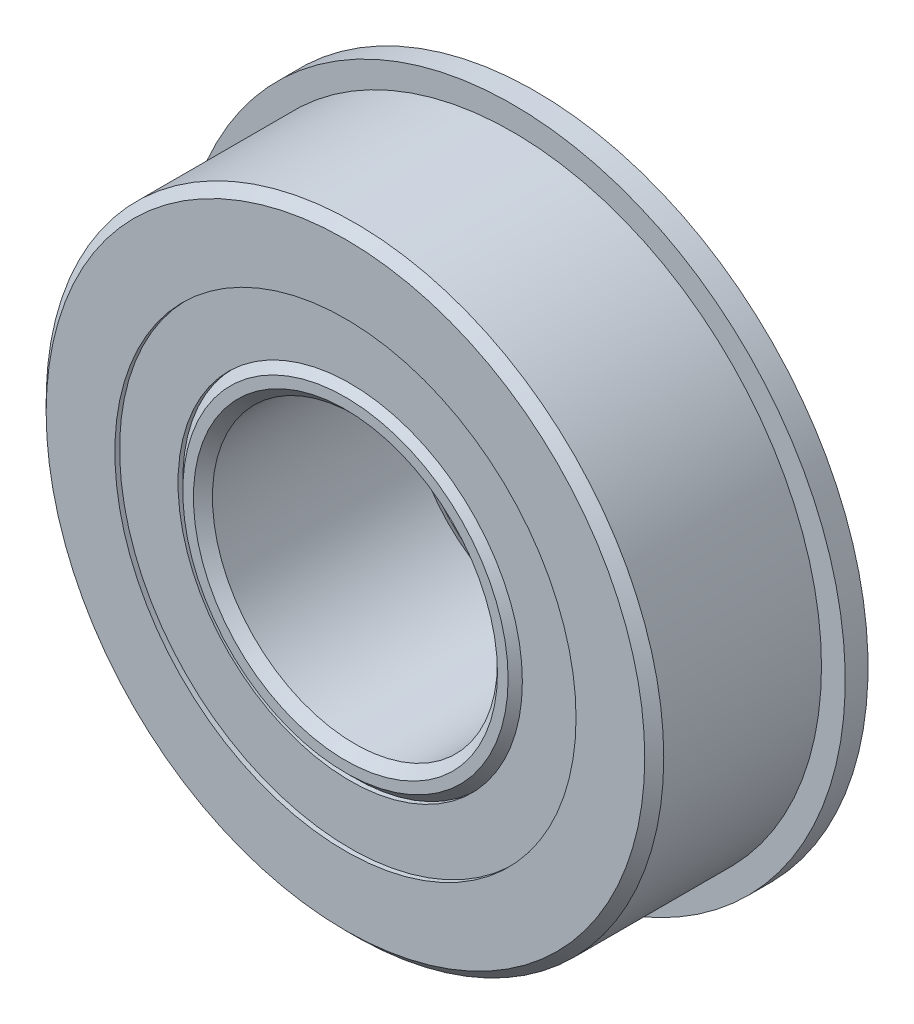
SolidWorks part; units mm, degrees
ref_plane "Front Plane" through (0, 0, 0) normal (0, 0, 1) x (1, 0, 0)
ref_plane "Top Plane" through (0, 0, 0) normal (0, 1, 0) x (1, 0, 0)
ref_plane "Right Plane" through (0, 0, 0) normal (1, 0, 0) x (0, 0, -1)
sketch "Sketch1" plane through (0, 0, 0) normal (1, 0, 0) x (0, 0, -1)
  line L0 (-6.35, 0) -> (6.35, 0) construction
  line L1 (0, 20.6375) -> (0, -20.6375) construction
  line L2 (5.715, 20.6375) -> (-5.715, 20.6375)
  line L3 (-5.715, 20.6375) -> (-6.35, 20.0025)
  line L4 (-6.35, 20.0025) -> (-6.35, 15.4104)
  line L5 (-6.35, 15.4104) -> (-4.2205, 15.4104)
  line L6 (6.35, 15.4104) -> (4.2205, 15.4104)
  line L7 (6.35, 20.0025) -> (6.35, 15.4104)
  line L8 (5.715, 20.6375) -> (6.35, 20.0025)
  line L9 (0, 20.6375) -> (0, 15.0813) construction
  line L10 (0, 15.0813) -> (0, 9.525) construction
  line L11 (6.35, 11.5062) -> (6.35, -11.5062) construction
  line L12 (-6.35, 9.525) -> (6.35, 9.525) construction
  line L13 (0, 10.8479) -> (0, 9.525) construction
  line L14 (0, 19.3146) -> (0, 20.6375) construction
  line L15 (6.35, 11.5062) -> (0, 11.5062) construction
  circle A1 centre (0, 15.0813) radius 4.2333 construction
  arc A2 (-4.2205, 15.4104) -> (4.2205, 15.4104) centre (0, 15.0813) cw
  point P14 (0, 9.525)
  point P22 (0, 10.8479)
  point P23 (0, 19.3146)
  dimension "D3" = 8.4667
  dimension "Width" = 12.7
  dimension "OD" = 41.275
  dimension "D1" = 45
  dimension "D2" = 0.635
  dimension "D4" = 23.0124
  dimension "D5" = 7.8084
  dimension "D6" = 3.9042
revolve "Revolve1" add sketch "Sketch1" angle 360 about L0
sketch "Sketch3" plane through (0, 0, 0) normal (1, 0, 0) x (0, 0, -1)
  line L1 (-6.35, 20.0025) -> (-6.35, 15.4104) construction
  line L2 (-5.715, 20.6375) -> (-6.35, 20.0025) construction
  line L3 (-6.35, 14.7521) -> (-6.35, 10.16) construction
  line L4 (-6.35, 10.16) -> (-6.35, 10.8712)
  line L5 (-6.35, 10.16) -> (-5.715, 9.525)
  line L6 (-5.715, 9.525) -> (7.3152, 9.525)
  line L7 (-6.35, 20.0025) -> (-6.35, -20.0025) construction
  line L8 (7.3152, 9.525) -> (7.9502, 10.16)
  line L9 (0, 0) -> (7.9502, 0) construction
  line L13 (5.715, 20.6375) -> (6.35, 20.0025) construction
  line L14 (-6.35, 10.8712) -> (-5.715, 11.5062)
  line L15 (-5.715, 11.5062) -> (-2.2672, 11.5062)
  line L16 (2.2672, 11.5062) -> (7.3152, 11.5062)
  line L17 (7.3152, 11.5062) -> (7.9502, 10.8712)
  line L18 (7.9502, 10.8712) -> (7.9502, 10.16)
  circle A0 centre (0, 15.0813) radius 4.2333 construction
  arc A1 (-2.2672, 11.5062) -> (2.2672, 11.5062) centre (0, 15.0813) ccw
  dimension "D1" = 45
  dimension "Ring Wd" = 14.3002
  dimension "Inner Ring OD" = 23.0124
revolve "Revolve3" add sketch "Sketch3" angle 360 about L0
sketch "Sketch6" plane through (0, 0, 0) normal (1, 0, 0) x (0, 0, -1)
  line L1 (6.35, 15.4104) -> (4.826, 15.4104)
  line L2 (6.35, 15.4104) -> (6.35, 22.225)
  line L3 (6.35, 22.225) -> (4.826, 22.225)
  line L4 (4.826, 15.4104) -> (4.826, 22.225)
  line L5 (6.35, 0) -> (-6.35, 0) construction
  dimension "Flange OD" = 44.45
  dimension "Flange Thickness" = 1.524
revolve "Revolve6" add sketch "Sketch6" angle 360 about L5
sketch "Sketch4" plane through (0, 0, 0) normal (1, 0, 0) x (0, 0, -1)
  line L0 (-4.2333, 15.0813) -> (4.2333, 15.0813)
  circle A0 centre (0, 15.0813) radius 4.2333 construction
  arc A1 (4.2333, 15.0813) -> (-4.2333, 15.0813) centre (0, 15.0813) ccw
revolve "Revolve4" add sketch "Sketch4" angle 360 about L0
ref_axis "Axis1" through (0, 0, -6.35) along (0, 0, 1)
pattern_circular "CirPattern1" count 12 every 30 about axis through (0, 0, -6.35) along (0, 0, 1) of bodies 104
sketch "Sketch5" plane through (0, 0, 0) normal (1, 0, 0) x (0, 0, -1)
  line L0 (-6.35, 15.4104) -> (-4.2205, 15.4104) construction
  line L1 (-6.0325, 15.4104) -> (-2.2672, 15.4104)
  line L2 (-6.0325, 15.4104) -> (-6.0325, 11.5062)
  line L3 (-6.0325, 11.5062) -> (-2.2672, 11.5062)
  line L4 (-2.2672, 15.4104) -> (-2.2672, 11.5062)
  line L6 (6.35, 15.4104) -> (4.2205, 15.4104) construction
  line L7 (6.0325, 15.4104) -> (2.2672, 15.4104)
  line L8 (6.0325, 15.4104) -> (6.0325, 11.5062)
  line L9 (6.0325, 11.5062) -> (2.2672, 11.5062)
  line L10 (2.2672, 15.4104) -> (2.2672, 11.5062)
  line L12 (-5.715, 20.6375) -> (-6.35, 20.0025) construction
  line L13 (6.35, 11.5062) -> (0, 11.5062) construction
  line L15 (-5.715, 11.5062) -> (-2.2672, 11.5062) construction
  line L16 (6.0325, 15.4104) -> (6.0325, 20.32) construction
  line L17 (5.715, 20.6375) -> (6.35, 20.0025) construction
  point P18 (-6.0325, 20.32)
revolve "Revolve5" add sketch "Sketch5" angle 360 about L0
ref_axis "Axis2" through (0, 0, -6.5718) along (0, 0, 1)
ref_plane "Plane1" through (0, 0, -4.826) normal (0, 0, 1) x (1, 0, 0)
equation "\"D2@Sketch1\" = \"Width@Sketch1\"*.05"
equation "\"D2@CirPattern1\" = 360/\"Balls@CirPattern1\""
equation "\"D4@Sketch1\"=\"Inner Ring OD@Sketch3\""
equation "\"D3@Sketch1\"=\"Width@Sketch1\"/1.5"
equation "\"D6@Sketch1\"=\"D5@Sketch1\"/2"
